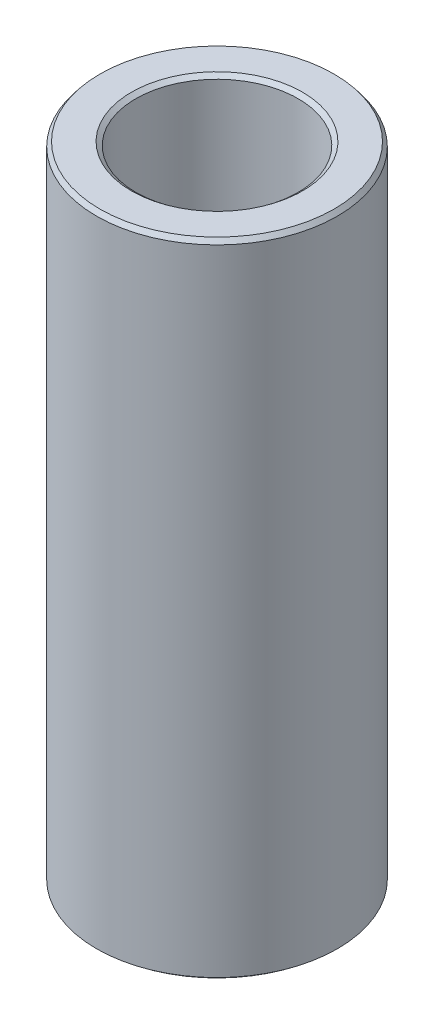
SolidWorks part; units mm, degrees
ref_plane "Front Plane" through (0, 0, 0) normal (0, 0, 1) x (1, 0, 0)
ref_plane "Top Plane" through (0, 0, 0) normal (0, 1, 0) x (1, 0, 0)
ref_plane "Right Plane" through (0, 0, 0) normal (1, 0, 0) x (0, 0, -1)
sketch "Sketch1" plane through (0, 0, 0) normal (0, 1, 0) x (1, 0, 0)
  circle A0 centre (0, 0) radius 7.5
  dimension "SLEEVE_OD" = 15
extrude "Boss-Extrude1" add sketch "Sketch1" along normal blind 39.9932
sketch "Sketch2" plane through (0, 0, 0) normal (0, 1, 0) x (1, 0, 0)
  circle A0 centre (0, 0) radius 5.0551
  dimension "BORE_D" = 10.1103
extrude "Cut-Extrude1" cut sketch "Sketch2" along normal through all
chamfer "Chamfer1" distance 0.272 angle 38.066 4 edges at (0, 39.9932, 5.0551) (0, 0, 5.0551) (0, 0, 7.5) (0, 39.9932, 7.5) first distance on face at (0, 39.9932, 5.0551) first distance on face at (0, 0, 5.0551) first distance on face at (0, 39.9932, 7.5)
